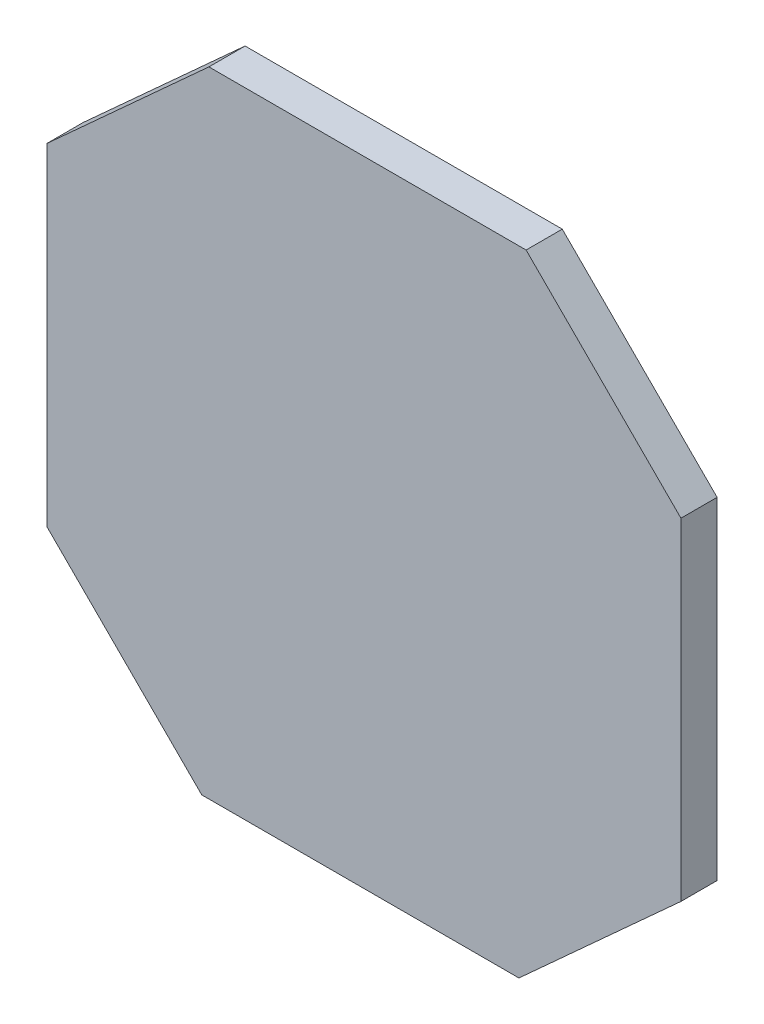
SolidWorks part; units mm, degrees
ref_plane "Front Plane" through (0, 0, 0) normal (0, 0, 1) x (1, 0, 0)
ref_plane "Top Plane" through (0, 0, 0) normal (0, 1, 0) x (1, 0, 0)
ref_plane "Right Plane" through (0, 0, 0) normal (1, 0, 0) x (0, 0, -1)
sketch "Sketch1" plane through (0, 0, 0) normal (0, 0, 1) x (1, 0, 0)
  line L0 (20.6787, 89.65) -> (-2.2589, 68.7965)
  line L1 (19.6614, -0.11) -> (64.5635, -0.11)
  line L2 (-2.2589, 21.8103) -> (-2.2589, 68.7965)
  line L3 (20.6787, 89.65) -> (65.5808, 89.65)
  line L4 (87.5011, 20.7434) -> (87.5011, 67.7296)
  line L5 (-2.2589, 21.8103) -> (19.6614, -0.11)
  line L6 (65.5808, 89.65) -> (87.5011, 67.7296)
  line L7 (87.5011, 20.7434) -> (64.5635, -0.11)
  dimension "D1" = 89.76
  dimension "D2" = 89.76
  dimension "D3" = 31
extrude "Boss-Extrude1" add sketch "Sketch1" along normal blind 5.12
equation "\"mdf\"=\"mdf@fmv1.assembly\""
equation "\"D1@Sketch1\" = 100-2*\"mdf\""
equation "\"D2@Sketch1\" = 100-2*\"mdf\""
equation "\"D1@Boss-Extrude1\"=\"mdf\""
